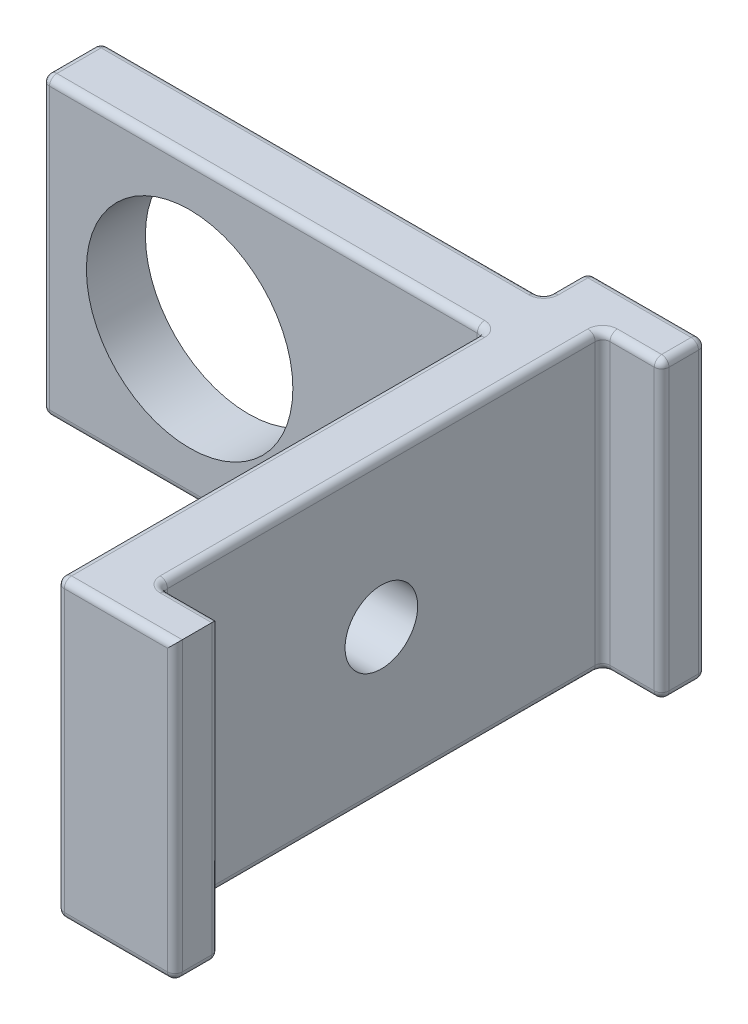
SolidWorks part; units mm, degrees
ref_plane "Piano frontale" through (0, 0, 0) normal (0, 0, 1) x (1, 0, 0)
ref_plane "Piano superiore" through (0, 0, 0) normal (0, 1, 0) x (1, 0, 0)
ref_plane "Piano destro" through (0, 0, 0) normal (1, 0, 0) x (0, 0, -1)
sketch "Schizzo1" plane through (0, 0, 0) normal (0, 0, 1) x (1, 0, 0)
  line L1 (-10, 10) -> (20, 10)
  line L2 (-10, 10) -> (-10, -10)
  line L3 (-10, -10) -> (20, -10)
  line L4 (20, 10) -> (20, -10)
  circle A1 centre (0, 0) radius 7
  point P10 (-9.1765, 0.989)
  dimension "D1" = 10
  dimension "D5" = 14
  dimension "D2" = 10
  dimension "D3" = 10
  dimension "D4" = 30
extrude "Estrusione-Estrusione1" add sketch "Schizzo1" along normal blind 4
sketch "Schizzo2" plane through (0, 0, 0) normal (0, 0, -1) x (-1, 0, 0)
  line L1 (-20, -10) -> (-24, -10)
  line L2 (-20, -10) -> (-20, 10)
  line L3 (-20, 10) -> (-24, 10)
  line L4 (-24, -10) -> (-24, 10)
extrude "Estrusione-Estrusione2" add sketch "Schizzo2" against normal blind 30
sketch "Schizzo3" plane through (0, 0, 30) normal (0, 0, 1) x (1, 0, 0)
  line L1 (20, -10) -> (28, -10)
  line L2 (20, -10) -> (20, 10)
  line L3 (20, 10) -> (28, 10)
  line L4 (28, -10) -> (28, 10)
extrude "Estrusione-Estrusione3" add sketch "Schizzo3" along normal blind 3
sketch "Schizzo4" plane through (0, 0, 0) normal (0, 0, -1) x (-1, 0, 0)
  line L0 (10, -10) -> (-24, -10) construction
  line L5 (-28, 10) -> (-20, 10)
  line L6 (-28, 10) -> (-28, -10)
  line L7 (-28, -10) -> (-20, -10)
  line L8 (-20, 10) -> (-20, -10)
extrude "Estrusione-Estrusione4" add sketch "Schizzo4" along normal blind 3
fillet "Raccordo1" radius 0.5 4 edges at (20, 0, 4) (20, 0, 0) (24, 0, 0) (24, 0, 30)
fillet "Raccordo2" radius 0.5 7 edges at (4.75, -10, 0) (20, -10, -1.75) (4.75, 10, 0) (19.8536, 10, -0.1464) (19.8536, -10, -0.1464) (28, 0, 0) (20, 10, -1.75)
fillet "Raccordo3" radius 0.5 7 edges at (26.25, -10, 30) (24, -10, 15) (28, -10, -1.75) (27.8536, -10, -0.1464) (24.1464, -10, 29.8536) (24.1464, -10, 0.1464) (26, -10, 0)
fillet "Raccordo4" radius 0.5 10 edges at (28, 0.25, 30) (28, -9.8536, 30.1464) (28, -10, 31.75) (26.25, 10, 30) (24, 10, 15) (28, 10, -1.75) (27.8536, 10, -0.1464) (24.1464, 10, 29.8536) (24.1464, 10, 0.1464) (26, 10, 0)
fillet "Raccordo5" radius 0.5 25 edges at (20.1464, -9.8536, -3) (-10, -9.8536, 0.1464) (19.8536, -10, 4.1464) (24, -10, -3) (20, 0, -3) (24, 10, -3) (20, 0, 33) (24, 10, 33) (23.75, -10, 33) (20, 10, 18.75) (19.8536, 10, 4.1464) (20, -10, 18.75) (-10, 0, 0) (-10, 0, 4) (4.75, -10, 4) (4.75, 10, 4) (20.1464, 9.8536, -3) (-10, 9.8536, 0.1464) (28, 0.25, 33) (27.8536, -9.8536, 33) (-10, -10, 2.25) (-10, 10, 2.25) (27.8536, -9.8536, -3) (28, 0, -3) (27.8536, 9.8536, -3)
sketch "Schizzo5" plane through (24, 0, 0) normal (1, 0, 0) x (0, 0, -1)
  line L0 (-30, 9.5) -> (-30, -9.5) construction
  circle A0 centre (-15, 0) radius 2.4622
  dimension "D1" = 15
extrude "Taglio-Estrusione1" cut sketch "Schizzo5" against normal blind 5
